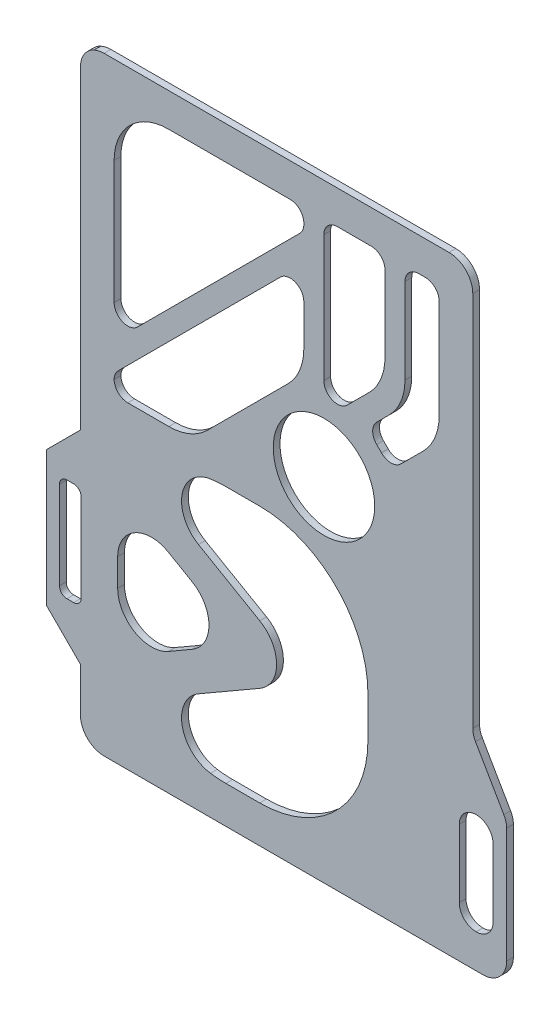
SolidWorks part; units mm, degrees
ref_plane "前视基准面" through (0, 0, 0) normal (0, 0, 1) x (1, 0, 0)
ref_plane "上视基准面" through (0, 0, 0) normal (0, 1, 0) x (1, 0, 0)
ref_plane "右视基准面" through (0, 0, 0) normal (1, 0, 0) x (0, 0, -1)
sketch "草图1" plane through (0, 0, 0) normal (0, 0, 1) x (1, 0, 0)
  line L27 (-1, -50) -> (-1.032, -50)
  line L28 (-34, 37.6372) -> (-34, 37.6623)
  line L29 (-36, 34.5) -> (-36, -12)
  line L30 (-36, -12) -> (-41, -17)
  line L31 (-41, -17) -> (-41, -37)
  line L32 (-41, -37) -> (-36, -42)
  line L33 (-36, -42) -> (-36, -48.5)
  line L34 (-32.5, -52) -> (-3, -52)
  line L35 (-38, -34.5) -> (-37, -34.5)
  line L36 (-36, -33.5) -> (-36, -20.5)
  line L37 (-37, -19.5) -> (-38, -19.5)
  line L38 (-39, -20.5) -> (-39, -33.5)
  line L40 (22, 37.9774) -> (-32.5, 37.9774)
  line L46 (-14.5, -46.5) -> (-9.5, -46.5)
  line L47 (-30.5, -24.5) -> (-30.5, -30.5)
  line L48 (-9.5, -8.5) -> (-14.5, -8.5)
  line L49 (6.5, -30.5) -> (6.5, -24.5)
  line L50 (11.9774, 31) -> (11.9774, 18.3848)
  line L51 (15, 33.0226) -> (14, 33.0226)
  line L52 (17.0226, 16.3137) -> (17.0226, 31)
  line L53 (11.3592, 7.3271) -> (14.6729, 10.6408)
  line L54 (7.7916, 8.0342) -> (8.4987, 7.3271)
  line L55 (9.6408, 12.7439) -> (7.7916, 10.8947)
  line L56 (7, 33.0226) -> (2, 33.0226)
  line L57 (9.0226, 19.8137) -> (9.0226, 31)
  line L58 (3.4302, 10.8982) -> (6.6729, 14.1408)
  line L59 (-0.0226, 31) -> (-0.0226, 12.3284)
  line L60 (-6.4302, 22.3592) -> (-30.4302, -1.6408)
  line L61 (-2.9774, 14.9289) -> (-2.9774, 20.9289)
  line L62 (-17.2561, -2.6729) -> (-5.3271, 9.2561)
  line L63 (-29, -5.0226) -> (-22.9289, -5.0226)
  line L64 (-27.5698, 5.3982) -> (-3.5698, 29.3982)
  line L65 (-31.0226, 25) -> (-31.0226, 6.8284)
  line L66 (-5, 33.0226) -> (-23, 33.0226)
  line L67 (-2.9774, 30.8284) -> (-2.9774, 31)
  line L69 (22, -2) -> (22, -22)
  line L70 (22, -22) -> (27, -30.6603)
  line L71 (27, -30.6603) -> (27, -52)
  line L72 (27, -52) -> (-3, -52)
  line L73 (22, 37.9774) -> (22, -2)
  line L74 (-38, -34.6) -> (-37, -34.6)
  line L75 (-35.9, -33.5) -> (-35.9, -20.5)
  line L76 (-37, -19.4) -> (-38, -19.4)
  line L77 (-39.1, -20.5) -> (-39.1, -33.5)
  arc A13 (-34, 37.6623) -> (-36, 34.5) centre (-32.5, 34.5) ccw
  arc A14 (-36, -48.5) -> (-32.5, -52) centre (-32.5, -48.5) ccw
  circle A15 centre (0, 0) radius 7.5
  arc A16 (-39, -33.5) -> (-38, -34.5) centre (-38, -33.5) ccw
  arc A17 (-37, -34.5) -> (-36, -33.5) centre (-37, -33.5) ccw
  arc A18 (-36, -20.5) -> (-37, -19.5) centre (-37, -20.5) ccw
  arc A19 (-38, -19.5) -> (-39, -20.5) centre (-38, -20.5) ccw
  arc A21 (-32.5, 37.9774) -> (-34, 37.6372) centre (-32.5, 34.5) ccw
  arc A24 (-30.5, -30.5) -> (-14.5, -46.5) centre (-14.5, -30.5) ccw
  arc A25 (-14.5, -8.5) -> (-30.5, -24.5) centre (-14.5, -24.5) ccw
  arc A26 (6.5, -24.5) -> (-9.5, -8.5) centre (-9.5, -24.5) ccw
  arc A27 (-9.5, -46.5) -> (6.5, -30.5) centre (-9.5, -30.5) ccw
  arc A28 (14, 33.0226) -> (11.9774, 31) centre (14, 31) ccw
  arc A29 (17.0226, 31) -> (15, 33.0226) centre (15, 31) ccw
  arc A30 (14.6729, 10.6408) -> (17.0226, 16.3137) centre (9, 16.3137) ccw
  arc A31 (8.4987, 7.3271) -> (11.3592, 7.3271) centre (9.9289, 8.7574) ccw
  arc A32 (7.7916, 10.8947) -> (7.7916, 8.0342) centre (9.2218, 9.4645) ccw
  arc A33 (9.6408, 12.7439) -> (11.9774, 18.3848) centre (4, 18.3848) ccw
  arc A34 (9.0226, 31) -> (7, 33.0226) centre (7, 31) ccw
  arc A35 (6.6729, 14.1408) -> (9.0226, 19.8137) centre (1, 19.8137) ccw
  arc A36 (-0.0226, 12.3284) -> (3.4302, 10.8982) centre (2, 12.3284) ccw
  arc A37 (2, 33.0226) -> (-0.0226, 31) centre (2, 31) ccw
  arc A38 (-2.9774, 20.9289) -> (-6.4302, 22.3592) centre (-5, 20.9289) ccw
  arc A39 (-5.3271, 9.2561) -> (-2.9774, 14.9289) centre (-11, 14.9289) ccw
  arc A40 (-22.9289, -5.0226) -> (-17.2561, -2.6729) centre (-22.9289, 3) ccw
  arc A41 (-31.0223, -3.0355) -> (-29, -5.0226) centre (-29, -3) ccw
  arc A42 (-30.4302, -1.6408) -> (-31.0223, -3.0355) centre (-29, -3.0711) ccw
  arc A43 (-31.0226, 6.8284) -> (-27.5698, 5.3982) centre (-29, 6.8284) ccw
  arc A44 (-23, 33.0226) -> (-31.0226, 25) centre (-23, 25) ccw
  arc A45 (-2.9774, 31) -> (-5, 33.0226) centre (-5, 31) ccw
  arc A46 (-3.5698, 29.3982) -> (-2.9774, 30.8284) centre (-5, 30.8284) ccw
  arc A47 (-37, -34.6) -> (-35.9, -33.5) centre (-37, -33.5) ccw
  arc A48 (-35.9, -20.5) -> (-37, -19.4) centre (-37, -20.5) ccw
  arc A49 (-38, -19.4) -> (-39.1, -20.5) centre (-38, -20.5) ccw
  arc A50 (-39.1, -33.5) -> (-38, -34.6) centre (-38, -33.5) ccw
  dimension "D3" = 5
  dimension "D1" = 58
  dimension "D2" = 150
  dimension "D4" = 30
  dimension "D5" = 0.1
  dimension "D6" = 50
extrude "凸台-拉伸1" add sketch "草图1" along normal blind 1 contours L40 A21 L28 A13 L29 L30 L31 L32 L33 A14 L34 L72 L71 L70 L69 A46 L64 A43 L65 A44 L66 A45 L67 A42 L60 A38 L61 A39 L62 A40 L63 A41 A37 L56 A34 L57 A35 L58 A36 L59 region at (-33.0196, 36.7913, 0)
fillet "圆角1" radius 3 2 edges at (27, -30.6603, 0.5) (22, -22, 0.5)
fillet "圆角2" radius 3.5 2 edges at (27, -52, 0.5) (22, 37.9774, 0.5)
sketch "草图2" plane through (0, 0, 0) normal (0, 0, -1) x (-1, 0, 0)
  line L0 (32.5, -52) -> (-23.5, -52) construction
  line L1 (-22.51, -47) -> (-22.49, -47)
  line L2 (-25, -44.51) -> (-25, -34.49)
  line L3 (-22.51, -32) -> (-22.49, -32)
  line L4 (-20, -44.51) -> (-20, -34.49)
  line L5 (-27, -31.4641) -> (-27, -48.5) construction
  arc A0 (-25, -44.51) -> (-22.51, -47) centre (-22.51, -44.51) ccw
  arc A1 (-22.49, -47) -> (-20, -44.51) centre (-22.49, -44.51) ccw
  arc A2 (-20, -34.49) -> (-22.49, -32) centre (-22.49, -34.49) ccw
  arc A3 (-22.51, -32) -> (-25, -34.49) centre (-22.51, -34.49) ccw
  point P10 (-25, -47)
  point P13 (-20, -47)
  point P16 (-20, -32)
  dimension "D5" = 2.49
  dimension "D1" = 5
  dimension "D2" = 15
  dimension "D3" = 5
  dimension "D4" = 2
extrude "切除-拉伸1" cut sketch "草图2" against normal blind 10
sketch "草图3" plane through (0, 0, 0) normal (0, 0, -1) x (-1, 0, 0)
  line L0 (12, -27.5) -> (29.3205, -17.5)
  line L1 (12, -27.5) -> (29.3205, -37.5)
  line L2 (2, -27.5) -> (30.7132, -10.9224)
  line L3 (2, -27.5) -> (30.7132, -44.0776)
  line L4 (-6.5, -27.5) -> (30.5, -27.5) construction
  line L5 (-6.5, -30.5) -> (-6.5, -24.5) construction
  line L6 (30.5, -24.5) -> (30.5, -30.5) construction
  line L7 (12, -8.5) -> (12, -46.5) construction
  line L8 (9.5, -8.5) -> (14.5, -8.5) construction
  line L9 (14.5, -46.5) -> (9.5, -46.5) construction
  line L10 (30.7132, -10.9224) -> (30.7132, -20.442)
  line L11 (30.7132, -34.558) -> (30.7132, -44.0776)
  arc A0 (29.3205, -37.5) -> (30.7132, -34.558) centre (12, -27.5) ccw
  arc A2 (30.7132, -20.442) -> (29.3205, -17.5) centre (12, -27.5) ccw
  dimension "D2" = 40
  dimension "D1" = 60
extrude "凸台-拉伸2" add sketch "草图3" against normal blind 1
fillet "圆角3" radius 5 6 edges at (-26.1647, -41.4515, 0.5) (-28.9812, -37.3041, 0.5) (-28.9812, -17.6959, 0.5) (-26.1647, -13.5485, 0.5) (-12, -27.5, 0.5) (-2, -27.5, 0.5)
